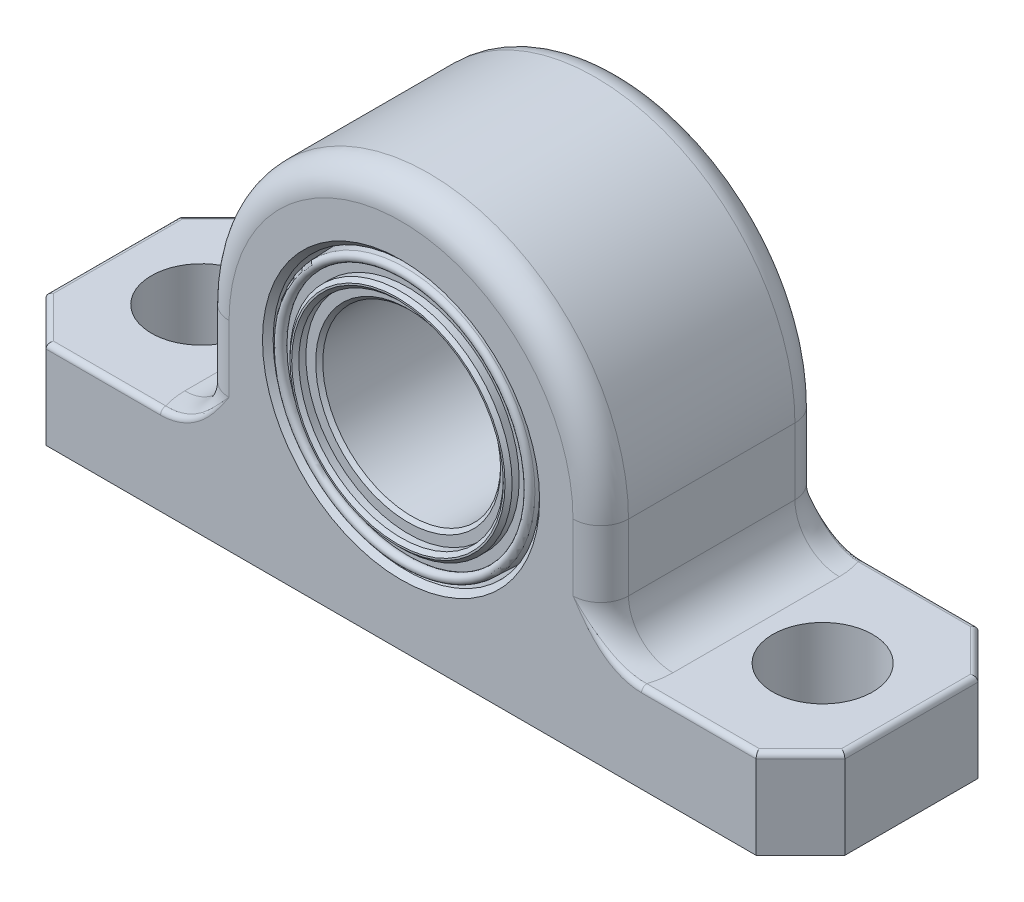
SolidWorks part; units mm, degrees
ref_plane "Front Plane" through (0, 0, 0) normal (0, 0, 1) x (1, 0, 0)
ref_plane "Top Plane" through (0, 0, 0) normal (0, 1, 0) x (1, 0, 0)
ref_plane "Right Plane" through (0, 0, 0) normal (1, 0, 0) x (0, 0, -1)
sketch "Sketch1" plane through (0, 0, 0) normal (0, 0, 1) x (1, 0, 0)
  line L0 (-28.575, 0) -> (28.575, 0)
  line L1 (28.575, 0) -> (28.575, 6.35)
  line L2 (-28.575, 0) -> (-28.575, 6.35)
  line L3 (-28.575, 6.35) -> (-14.2875, 6.35)
  line L4 (28.575, 6.35) -> (14.2875, 6.35)
  line L5 (-14.2875, 6.35) -> (-14.2875, 14.2875)
  line L6 (14.2875, 6.35) -> (14.2875, 14.2875)
  line L7 (0, 0) -> (0, 28.575) construction
  line L8 (4.4991, 18.7866) -> (10.1028, 24.3903) construction
  line L9 (4.4991, 18.7866) -> (5.6198, 19.9073) construction
  line L10 (5.6198, 19.9073) -> (6.7406, 21.0281) construction
  line L11 (6.7406, 21.0281) -> (7.8613, 22.1488) construction
  line L12 (7.8613, 22.1488) -> (8.9821, 23.2696) construction
  line L13 (8.9821, 23.2696) -> (10.1028, 24.3903) construction
  circle A0 centre (0, 14.2875) radius 6.3627
  arc A1 (14.2875, 14.2875) -> (-14.2875, 14.2875) centre (0, 14.2875) ccw
  circle A2 centre (0, 14.2875) radius 9.5326 construction
  point P16 (6.7406, 21.0281)
  point P17 (0, 20.6502)
  point P18 (0, 23.8201)
  dimension "ID" = 12.7254
  dimension "Overall Height" = 28.575
  dimension "Overall Length" = 57.15
  dimension "CAD B" = 6.35
  dimension "Center Height" = 14.2875
  dimension "D1" = 45
sketch "Sketch2" plane through (0, 0, 0) normal (0, 1, 0) x (1, 0, 0)
  line L0 (-22.225, 0) -> (22.225, 0) construction
  line L1 (-28.575, -7.9375) -> (28.575, 7.9375) construction
  line L2 (-28.575, 7.9375) -> (28.575, 7.9375)
  line L3 (-28.575, 7.9375) -> (-28.575, -7.9375)
  line L4 (-28.575, -7.9375) -> (28.575, -7.9375)
  line L5 (28.575, 7.9375) -> (28.575, -7.9375)
  circle A0 centre (-22.225, 0) radius 3.5719
  circle A1 centre (22.225, 0) radius 3.5719
sketch "Sketch3" plane through (0, 0, 0) normal (0, 0, 1) x (1, 0, 0)
  line L0 (-28.575, 0) -> (-28.575, 6.35) construction
  line L1 (-28.575, 0) -> (28.575, 0) construction
  line L2 (-28.575, 6.35) -> (-14.2875, 6.35) construction
  line L3 (28.575, 6.35) -> (14.2875, 6.35) construction
  line L4 (28.575, 0) -> (28.575, 6.35) construction
  line L5 (14.2875, 6.35) -> (14.2875, 14.2875) construction
  line L6 (-14.2875, 6.35) -> (-14.2875, 14.2875) construction
  line L7 (-28.575, 0) -> (-28.575, 6.35)
  line L8 (-28.575, 0) -> (28.575, 0)
  line L9 (-28.575, 6.35) -> (-14.2875, 6.35)
  line L10 (28.575, 6.35) -> (14.2875, 6.35)
  line L11 (28.575, 0) -> (28.575, 6.35)
  line L12 (14.2875, 6.35) -> (14.2875, 14.2875)
  line L13 (-14.2875, 6.35) -> (-14.2875, 14.2875)
  arc A0 (14.2875, 14.2875) -> (-14.2875, 14.2875) centre (0, 14.2875) ccw construction
  circle A1 centre (0, 14.2875) radius 9.5326 construction
  arc A2 (14.2875, 14.2875) -> (-14.2875, 14.2875) centre (0, 14.2875) ccw
  circle A3 centre (0, 14.2875) radius 9.5326
extrude "Boss-Extrude1" add sketch "Sketch3" against normal up to vertex (7.9375 mm away) and the other way up to vertex (7.9375 mm away) up to point (-28.575, 0, -7.9375) other way up to point (-28.575, 0, 7.9375)
sketch "Sketch4" plane through (0, 0, 0) normal (0, 1, 0) x (1, 0, 0)
  circle A0 centre (-22.225, 0) radius 3.5719 construction
  circle A1 centre (22.225, 0) radius 3.5719 construction
  circle A2 centre (-22.225, 0) radius 3.5719
  circle A3 centre (22.225, 0) radius 3.5719
extrude "Cut-Extrude1" cut sketch "Sketch4" along normal through all
chamfer "Chamfer1" distance 3.175 angle 45 4 edges at (-28.575, 3.175, -7.9375) (28.575, 3.175, 7.9375) (28.575, 3.175, -7.9375) (-28.575, 3.175, 7.9375)
fillet "Fillet1" radius 1.9844 6 edges at (-14.2875, 10.3188, -7.9375) (0, 28.575, -7.9375) (-14.2875, 10.3188, 7.9375) (0, 28.575, 7.9375) (14.2875, 10.3187, -7.9375) (14.2875, 10.3187, 7.9375)
fillet "Fillet2" radius 3.175 6 edges at (-13.7063, 6.35, -7.3563) (-13.7063, 6.35, 7.3563) (13.7063, 6.35, -7.3563) (13.7063, 6.35, 7.3563) (-14.2875, 6.35, 0) (14.2875, 6.35, 0)
chamfer "Chamfer2" distance 0.381 angle 45 2 edges at (9.5326, 14.2875, 7.9375) (9.5326, 14.2875, -7.9375)
fillet "Fillet3" radius 0.381 14 edges at (-15.7758, 6.5694, -7.9375) (-15.7758, 6.5694, 7.9375) (15.7758, 6.5694, -7.9375) (15.7758, 6.5694, 7.9375) (-21.2328, 6.35, -7.9375) (-26.9875, 6.35, -6.35) (-28.575, 6.35, 0) (-26.9875, 6.35, 6.35) (-21.2328, 6.35, 7.9375) (21.2328, 6.35, -7.9375) (26.9875, 6.35, -6.35) (28.575, 6.35, 0) (26.9875, 6.35, 6.35) (21.2328, 6.35, 7.9375)
sketch "Sketch5" plane through (0, 0, 0) normal (1, 0, 0) x (0, 0, -1)
  line L1 (-7.9375, 23.8201) -> (7.9375, 23.8201)
  line L2 (-7.9375, 23.8201) -> (-7.9375, 20.6502)
  line L3 (-7.9375, 20.6502) -> (7.9375, 20.6502)
  line L4 (7.9375, 23.8201) -> (7.9375, 20.6502)
sketch "Sketch6" plane through (0, 0, 0) normal (1, 0, 0) x (0, 0, -1)
  line L0 (0, 23.8201) -> (7.9375, 23.8201)
  line L1 (0, 20.6502) -> (0, 21.1785) construction
  line L2 (0, 23.8201) -> (-7.6244, 23.5539)
  line L3 (-7.9375, 23.8201) -> (-7.9375, 20.6502) construction
  line L4 (-7.4295, 22.9622) -> (-7.4295, 22.2352)
  line L5 (-7.4295, 22.2352) -> (-8.1915, 22.2352)
  line L6 (-8.1915, 22.2352) -> (-8.1915, 21.6046)
  line L7 (-8.1915, 21.6046) -> (-7.4295, 21.6046)
  line L8 (-7.4295, 21.6046) -> (-7.4295, 20.6502)
  line L9 (-7.9375, 20.6502) -> (7.9375, 20.6502) construction
  line L10 (-7.4295, 20.6502) -> (5.9055, 20.6502)
  line L11 (7.9375, 23.8201) -> (7.9375, 22.9622)
  line L12 (7.9375, 23.8201) -> (7.9375, 20.6502) construction
  line L13 (7.9375, 22.9622) -> (4.1275, 22.9622)
  line L14 (4.1275, 22.9622) -> (4.1275, 22.2352)
  line L15 (4.1275, 22.2352) -> (6.6675, 22.2352)
  line L16 (6.6675, 22.2352) -> (6.6675, 21.6046)
  line L17 (6.6675, 21.6046) -> (5.9055, 21.6046)
  line L18 (5.9055, 21.6046) -> (5.9055, 20.6502)
  line L19 (0, 0) -> (0, 28.575) construction
  line L20 (-7.9375, 14.2875) -> (7.9375, 14.2875) construction
  line L21 (-7.9375, 0) -> (-7.9375, 5.969) construction
  line L22 (0, 21.1785) -> (0, 21.7068) construction
  line L23 (0, 21.7068) -> (0, 22.2352) construction
  line L24 (0, 22.2352) -> (0, 22.7635) construction
  line L25 (0, 22.7635) -> (0, 23.2918) construction
  line L26 (0, 23.2918) -> (0, 23.8201) construction
  line L27 (-7.4295, 22.2352) -> (4.1275, 22.2352) construction
  arc A0 (-7.6244, 23.5539) -> (-7.4295, 22.9622) centre (-7.6131, 23.2297) ccw
  dimension "D8" = 0.3244
  dimension "D1" = 2
  dimension "D2" = 0.254
  dimension "D3" = 0.762
  dimension "D5" = 1.27
  dimension "D6" = 2.54
  dimension "D9" = 14.6342
revolve "Revolve1" add sketch "Sketch6" angle 360 about L20
chamfer "Chamfer3" distance 0.254 angle 45 6 edges at (7.3171, 14.2875, -6.6675) (7.9477, 14.2875, -6.6675) (6.3627, 14.2875, 7.4295) (6.3627, 14.2875, -5.9055) (7.9477, 14.2875, 8.1915) (7.3171, 14.2875, 8.1915)
equation "\"D1@Fillet1\"=\"Overall Width@Sketch2\"/8"
equation "\"D9@Sketch6\"=\"ID@Sketch1\"*1.15"
